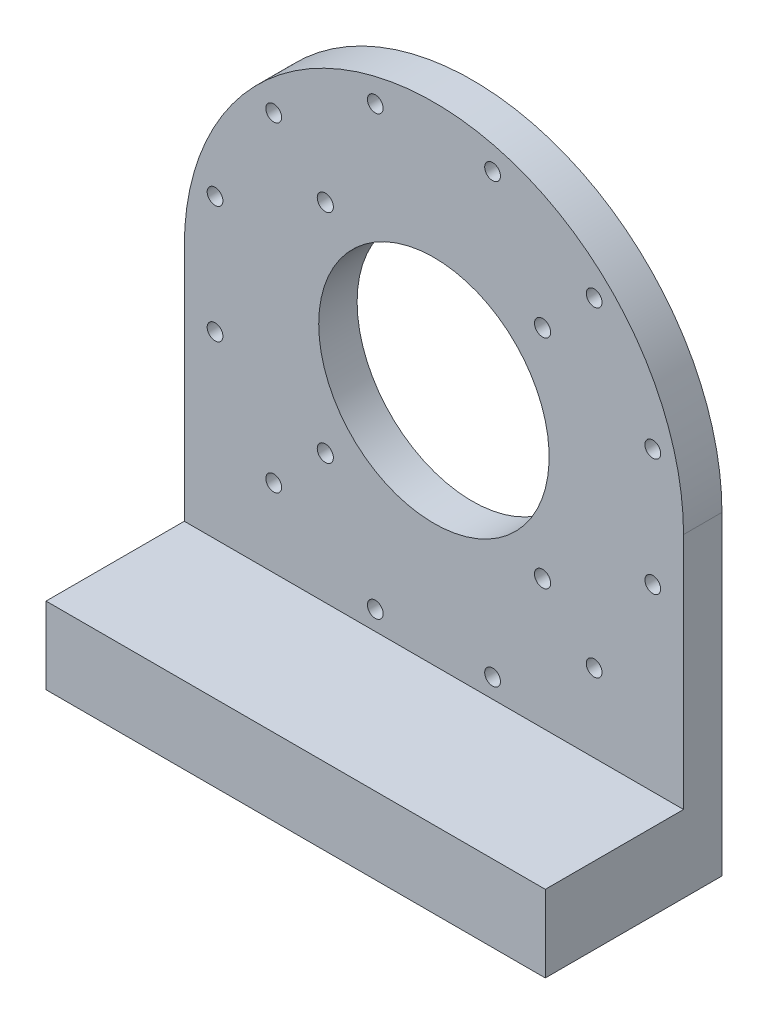
SolidWorks part; units mm, degrees
ref_plane "Front Plane" through (0, 0, 0) normal (0, 0, 1) x (1, 0, 0)
ref_plane "Top Plane" through (0, 0, 0) normal (0, 1, 0) x (1, 0, 0)
ref_plane "Right Plane" through (0, 0, 0) normal (1, 0, 0) x (0, 0, -1)
sketch "Sketch1" plane through (0, 0, -97.5071) normal (0, 0, -1) x (-1, 0, 0)
  line L0 (-154.0728, 47.2587) -> (-154.0728, -14.7413)
  line L1 (-24.0728, 47.2587) -> (-24.0728, -14.7413)
  line L2 (-154.0728, -14.7413) -> (-24.0728, -14.7413)
  line L4 (-154.0728, -14.7413) -> (-24.0728, -14.7413)
  line L5 (-154.0728, -14.7413) -> (-154.0728, -34.7413)
  line L6 (-154.0728, -34.7413) -> (-24.0728, -34.7413)
  line L7 (-24.0728, -14.7413) -> (-24.0728, -34.7413)
  line L9 (-24.0728, -14.7413) -> (-24.0728, -34.7413)
  line L13 (-154.0728, -34.7413) -> (-154.0728, -14.7413)
  arc A0 (-24.0728, 47.2587) -> (-154.0728, 47.2587) centre (-89.0728, 47.2587) ccw
  line M11 (-116.0728, 53.2587) -> (-116.0728, 41.2587)
  line M12 (-116.0728, 41.2587) -> (-149.777, 41.2587)
  arc M13 (-149.777, 41.2587) -> (-149.777, 53.2587) centre (-89.0728, 47.2587) ccw
  line M14 (-149.777, 53.2587) -> (-116.0728, 53.2587)
  circle M15 centre (-117.3571, 18.9744) radius 2.1
  circle M16 centre (-60.7885, 18.9744) radius 2.1
  circle M17 centre (-60.7885, 75.543) radius 2.1
  circle M18 centre (-117.3571, 75.543) radius 2.1
  circle M19 centre (-104.3431, 104.2483) radius 1.575
  circle M20 centre (-146.0624, 62.529) radius 1.575
  circle M21 centre (-130.7921, 5.5394) radius 1.575
  circle M22 centre (-73.8025, -9.7309) radius 1.575
  circle M23 centre (-32.0832, 31.9884) radius 1.575
  circle M24 centre (-32.0832, 62.529) radius 1.575
  circle M25 centre (-47.3535, 88.978) radius 1.575
  circle M26 centre (-47.3535, 5.5394) radius 1.575
  circle M27 centre (-104.3431, -9.7309) radius 1.575
  circle M28 centre (-146.0624, 31.9884) radius 1.575
  circle M29 centre (-130.7921, 88.978) radius 1.575
  circle M30 centre (-73.8025, 104.2483) radius 1.575
  circle M31 centre (-89.0728, 47.2587) radius 15
  dimension "D3" = 65
  dimension "D1" = 20
  dimension "D2" = 62
  dimension "D4" = 130
extrude "Boss-Extrude1" add sketch "Sketch1" along normal blind 10 contours L1 A0 L0 L2 M11 M14 M13 M12 | L7 L2 L5 L6 | M14 M11 M12 M13 M15 M17 M19 M21 M23 M25 M27 M29 M31 M30 M28 M26 M24 M22 M20 M18 M16 region at (89.0728, 110.4413, -97.5071) region at (89.0728, -24.7413, -97.5071) region at (132.9249, 54.982, -97.5071)
extrude "Boss-Extrude2" add sketch "Sketch1<3>" against normal blind 36 contours L7 L2 L5 L6 region at (89.0728, -24.7413, -97.5071)
sketch "Sketch1<3>" plane through (0, 0, -97.5071) normal (0, 0, -1) x (-1, 0, 0) same geometry as "Sketch1"
sketch "Sketch2" plane through (0, 0, -107.5071) normal (0, 0, -1) x (-1, 0, 0)
  circle A0 centre (-89.0728, 47.2587) radius 30
  dimension "D1" = 60
extrude "Cut-Extrude1" cut sketch "Sketch2" against normal blind 36
sketch "Sketch4" plane through (0, 0, -107.5071) normal (0, 0, -1) x (-1, 0, 0)
  circle A0 centre (-73.8025, 104.2483) radius 2.05
  circle A1 centre (-47.3535, 88.978) radius 2.05
  circle A2 centre (-32.0832, 62.529) radius 2.05
  circle A3 centre (-32.0832, 31.9884) radius 2.05
  circle A4 centre (-47.3535, 5.5394) radius 2.05
  circle A5 centre (-73.8025, -9.7309) radius 2.05
  circle A6 centre (-104.3431, -9.7309) radius 2.05
  circle A7 centre (-130.7921, 5.5394) radius 2.05
  circle A8 centre (-146.0624, 31.9884) radius 2.05
  circle A9 centre (-146.0624, 62.529) radius 2.05
  circle A10 centre (-130.7921, 88.978) radius 2.05
  circle A11 centre (-104.3431, 104.2483) radius 2.05
  point P28 (-89.0728, 47.2587)
  dimension "D1" = 4.1
  dimension "D2" = 12
extrude "Cut-Extrude2" cut sketch "Sketch4" against normal through all
equation "\"helloi\"= 123"
